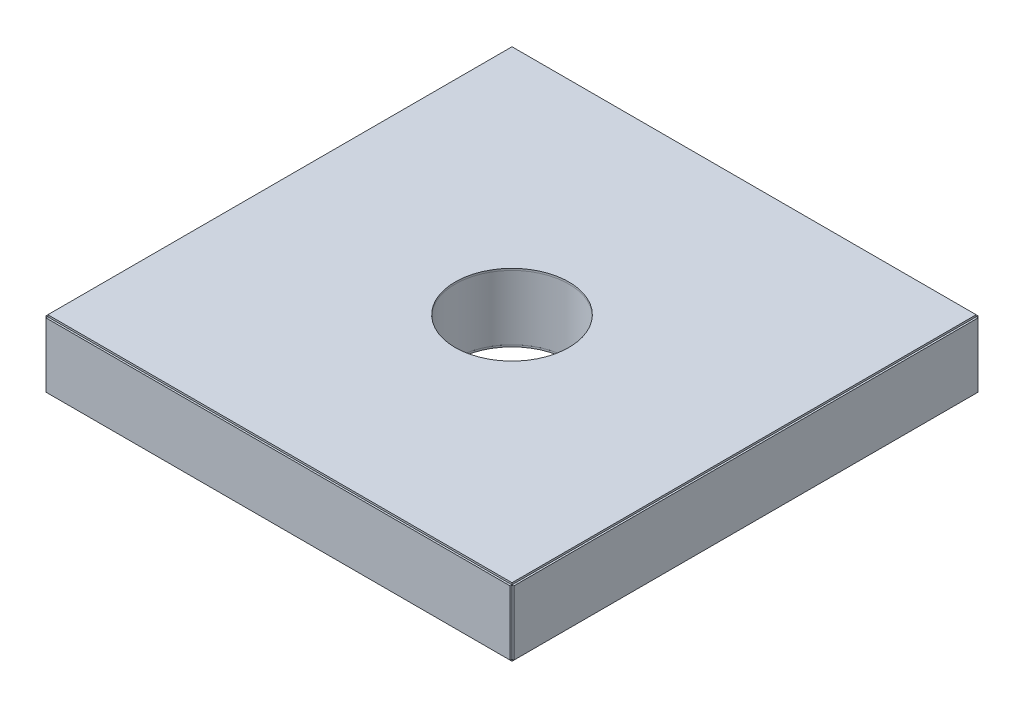
SolidWorks part; units mm, degrees
ref_plane "Front Plane" through (0, 0, 0) normal (0, 0, 1) x (1, 0, 0)
ref_plane "Top Plane" through (0, 0, 0) normal (0, 1, 0) x (1, 0, 0)
ref_plane "Right Plane" through (0, 0, 0) normal (1, 0, 0) x (0, 0, -1)
sketch "Sketch1" plane through (0, 0, 0) normal (0, 1, 0) x (1, 0, 0)
  line L1 (0, 0) -> (641.1, 0)
  line L2 (0, 0) -> (0, 641.1)
  line L3 (0, 641.1) -> (641.1, 641.1)
  line L4 (641.1, 0) -> (641.1, 641.1)
  dimension "D1" = 641.1
  dimension "D2" = 641.1
extrude "Boss-Extrude1" add sketch "Sketch1" along normal blind 2.54
sketch "Sketch2" plane through (0, 2.54, 0) normal (0, 1, 0) x (1, 0, 0)
  line L0 (0, 0) -> (641.1, 641.1) construction
  line L2 (0, 0) -> (641.1, 0)
  line L3 (0, 0) -> (0, 641.1)
  line L4 (0, 641.1) -> (0, 0)
  line L5 (0, 0) -> (641.1, 0)
  line L6 (641.1, 0) -> (641.1, 641.1)
  line L7 (641.1, 641.1) -> (0, 641.1)
  line L8 (0, 641.1) -> (0, 0)
  line L9 (0, 0) -> (641.1, 0)
  line L10 (641.1, 0) -> (641.1, 641.1)
  line L11 (641.1, 641.1) -> (0, 641.1)
  line L12 (0, 641.1) -> (641.1, 641.1)
  line L13 (641.1, 0) -> (641.1, 641.1)
  line L14 (0, 0) -> (641.1, 641.1) construction
  line L15 (0, 641.1) -> (641.1, 0) construction
  point P2 (320.55, 320.55)
  point P4 (2.9007, 2.9007)
  point P9 (641.1, 638.3023)
  line M9 (0, 641.1) -> (0, 0)
  line M10 (0, 0) -> (641.1, 0)
  line M11 (641.1, 0) -> (641.1, 641.1)
  line M12 (641.1, 641.1) -> (0, 641.1)
  dimension "D1" = 0
extrude "Boss-Extrude2" add sketch "Sketch2" along normal blind 88.9 separate body contours M12 M9 M10 M11 | L2 L13 L12 L3 M9 M12 M11 M10 | L8 L9 L10 L11 | L3 L2 L13 L12 region at (320.55, 2.54, -320.55)
sketch "Sketch3" plane through (0, 0, 0) normal (0, 0, 1) x (1, 0, 0)
  line L4 (0, 2.54) -> (641.1, 2.54)
  line L5 (641.1, 2.54) -> (641.1, 91.44)
  line L6 (641.1, 91.44) -> (0, 91.44)
  line L7 (0, 91.44) -> (0, 2.54)
  line L8 (0, 2.54) -> (641.1, 2.54)
  line L9 (641.1, 2.54) -> (641.1, 91.44)
  line L10 (641.1, 91.44) -> (0, 91.44)
  line L11 (0, 91.44) -> (0, 2.54)
  dimension "D1" = 0
extrude "Boss-Extrude3" add sketch "Sketch3" along normal blind 2.54 separate body
ref_point "Point2"
ref_axis "Axis1" through (320.55, 91.44, -320.55) along (0, 1, 0)
pattern_circular "CirPattern1" count 4 over 360 about axis through (320.55, 91.44, -320.55) along (0, 1, 0) of bodies 103
sketch "Sketch5" plane through (0, 91.44, 0) normal (0, 1, 0) x (1, 0, 0)
  circle A0 centre (320.55, 320.55) radius 78.5
  dimension "D1" = 157
extrude "Cut-Extrude1" cut sketch "Sketch5" against normal through all
ref_plane "Plane1" through (320.55, 0, 0) normal (-1, 0, 0) x (0, 0, 1)
sketch "Sketch7" plane through (0, 91.44, 0) normal (0, 1, 0) x (1, 0, 0)
  line L4 (641.1, 641.1) -> (0, 641.1)
  line L5 (641.1, 0) -> (641.1, 641.1)
  line L6 (641.1, 641.1) -> (0, 641.1)
  line L7 (0, 641.1) -> (0, 0)
  line L8 (0, 0) -> (641.1, 0)
  line L9 (641.1, 0) -> (641.1, 641.1)
  line L11 (641.1, 641.1) -> (0, 641.1)
  line L12 (0, 641.1) -> (0, 0)
  line L13 (0, 0) -> (641.1, 0)
  line L15 (0, 641.1) -> (0, 0)
  line L16 (0, 0) -> (641.1, 0)
  line L17 (641.1, 0) -> (641.1, 641.1)
  line L18 (641.1, 641.1) -> (0, 641.1)
  line L19 (0, 641.1) -> (0, 0)
  line L20 (0, 0) -> (641.1, 0)
  line L21 (641.1, 0) -> (641.1, 641.1)
  line M8 (641.1, 641.1) -> (0, 641.1)
  line M9 (0, 641.1) -> (0, 0)
  line M10 (0, 0) -> (641.1, 0)
  circle M12 centre (320.55, 320.55) radius 78.5
  line M17 (641.1, 0) -> (641.1, 641.1)
  dimension "D1" = 0
  dimension "D2" = 0
extrude "Boss-Extrude4" add sketch "Sketch7" along normal blind 2.54 separate body contours M17 M8 M9 M10 M12 region at (632.0335, 91.44, -320.55)
